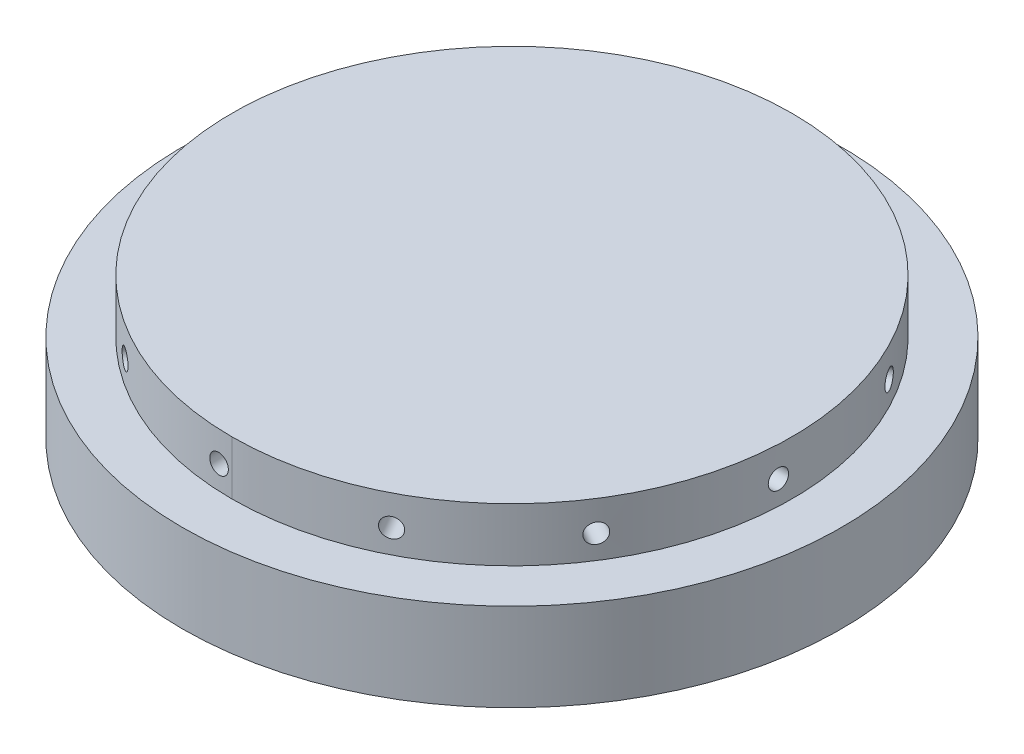
SolidWorks part; units mm, degrees
ref_plane "Front Plane" through (0, 0, 0) normal (0, 0, 1) x (1, 0, 0)
ref_plane "Top Plane" through (0, 0, 0) normal (0, 1, 0) x (1, 0, 0)
ref_plane "Right Plane" through (0, 0, 0) normal (1, 0, 0) x (0, 0, -1)
sketch "Sketch1" plane through (0, 0, 0) normal (0, 1, 0) x (1, 0, 0)
  circle A0 centre (0, 0) radius 64.77
  circle A1 centre (0, 0) radius 76.2
  circle A2 centre (0, 0) radius 56.1975
  circle A4 centre (0, 0) radius 62.865
  dimension "D1" = 152.4
  dimension "D3" = 112.395
  dimension "D2" = 129.54
  dimension "D4" = 13.335
extrude "Boss-Extrude1" add sketch "Sketch1" along normal blind 17.526 contours A0 A2 | A0 A4 region at (-62.938, 0, 0) region at (-61.0869, 0, 0)
extrude "Boss-Extrude2" add sketch "Sketch1<4>" along normal blind 5.08 and the other way blind 15.24 contours A1 A0 | A0 A4 region at (-62.938, 0, 0) region at (-74.0447, 0, 0)
sketch "Sketch1<4>" plane through (0, 0, 0) normal (0, 1, 0) x (1, 0, 0) same geometry as "Sketch1"
sketch "Sketch3" plane through (0, -15.24, 0) normal (0, -1, 0) x (1, 0, 0)
  line L0 (0, 0) -> (-65.7887, 5.7558) construction
  line L1 (0, 0) -> (0, 69.85) construction
  line L2 (0, 0) -> (48.9804, 58.3726)
  line L3 (0, 0) -> (13.232, 75.0424)
  line L4 (-13.335, -54.5925) -> (-13.335, -60.117)
  line L5 (13.335, -54.5925) -> (13.335, -60.117)
  line L6 (-13.335, -60.117) -> (13.335, -60.117)
  line L7 (-13.335, -60.117) -> (-13.335, -61.4344)
  line L8 (-23.7501, -50.9322) -> (-26.5679, -56.975)
  line L9 (0, 0) -> (-23.7501, -50.9322) construction
  line L10 (-65.2934, 11.4174) -> (-61.874, 11.1182)
  line L11 (-66.284, 0.0941) -> (-62.8647, -0.205)
  line L12 (-66.0236, -5.8708) -> (-62.6433, -5.2748)
  line L13 (-64.0498, -17.0646) -> (-60.6695, -16.4686)
  line L14 (-65.0367, -11.4677) -> (0, 0) construction
  line L15 (27.9275, 60.1135) -> (26.7536, 56.8881)
  line L16 (17.2465, 64.0011) -> (16.0725, 60.7757)
  line L17 (38.0961, -54.2427) -> (35.8898, -51.6133)
  line L18 (46.8033, -46.9365) -> (44.597, -44.3071)
  line L19 (-3.0468, 69.7835) -> (0, 0) construction
  line L20 (0, 0) -> (-21.0043, 66.6171) construction
  circle A0 centre (-65.7887, 5.7558) radius 5.6833
  circle A1 centre (-3.0468, 69.7835) radius 1.3589
  circle A2 centre (0, 0) radius 76.2 construction
  circle A5 centre (0, 0) radius 56.1975 construction
  arc A7 (-26.5679, -56.975) -> (-13.335, -61.4344) centre (0, 0) ccw
  arc A9 (-23.7501, -50.9322) -> (-13.335, -54.5925) centre (0, 0) ccw
  circle A10 centre (-65.7887, 5.7558) radius 2.5083
  circle A11 centre (-65.0367, -11.4677) radius 5.6832
  circle A13 centre (-65.0367, -11.4677) radius 2.5082
  circle A14 centre (0, 0) radius 62.865 construction
  circle A15 centre (22.587, 62.0573) radius 5.6832
  circle A16 centre (22.587, 62.0573) radius 2.5082
  circle A17 centre (42.4497, -50.5896) radius 5.6832
  circle A18 centre (42.4497, -50.5896) radius 2.5082
  arc A19 (-62.6433, -5.2748) -> (-60.6695, -16.4686) centre (0, 0) ccw
  circle A20 centre (-21.0043, 66.6171) radius 1.5
  circle A21 centre (0, 0) radius 62.865
  point P0 (0, -60.117)
  point P38 (0, 0)
  point P56 (0, 0)
  circle M49 centre (0, 0) radius 62.865
  dimension "D4" = 11.3665
  dimension "D5" = 2.7178
  dimension "D11" = 5.0165
  dimension "D17" = 3
  dimension "D1" = 66.04
  dimension "D3" = 69.85
  dimension "D6" = 30
  dimension "D7" = 10
  dimension "D9" = 26.67
  dimension "D8" = 5.5245
  dimension "D10" = 25
  dimension "D2" = 82.5
  dimension "D15" = 2.5
  dimension "D16" = 15
  dimension "D12" = 15
  dimension "D14" = 3
extrude "Cut-Extrude1" cut sketch "Sketch3" against normal blind 1.8415 contours A11 A13 M49 | A11 L13 M49 | A13 | A11 L12 M49 | A0 A10 M49 | A10 | A0 L11 M49 | A0 L10 M49 region at (-62.774, -15.24, 10.8743) region at (-63.6243, -15.24, 10.8507) region at (-63.7086, -15.24, 0.1915) region at (-63.4495, -15.24, -5.7433) region at (-64.265, -15.24, -5.9885) region at (-61.5874, -15.24, -16.304) region at (-65.7887, -15.24, 5.7558) region at (-65.0367, -15.24, -11.4677)
extrude "Cut-Extrude2" cut sketch "Sketch3<3>" against normal blind 12.7 contours A1 region at (-3.0468, -15.24, 69.7835)
sketch "Sketch3<3>" plane through (0, -15.24, 0) normal (0, -1, 0) x (1, 0, 0) same geometry as "Sketch3"
sketch "Sketch6" plane through (0, -13.3985, 0) normal (0, -1, 0) x (1, 0, 0)
  line L0 (-65.0367, -11.4677) -> (0, 0) construction
  line L1 (0, 0) -> (-65.7887, 5.7558) construction
  arc A0 (-65.2934, 11.4174) -> (-66.284, 0.0941) centre (-65.7887, 5.7558) ccw construction
  arc A1 (-65.2934, 11.4174) -> (-66.284, 0.0941) centre (-65.7887, 5.7558) ccw
  circle A2 centre (-65.7887, 5.7558) radius 2.5083
  circle A3 centre (-65.0367, -11.4677) radius 2.5082
  point P9 (0, 0)
  dimension "D1" = 5.0165
  dimension "D3" = 15
  dimension "D2" = 2
extrude "Cut-Extrude4" cut sketch "Sketch6" against normal blind 12.5095 contours A3 | A2 region at (-65.0367, -13.3985, -11.4677)
pattern_circular "CirPattern2" count 12 over 360 about axis through (0, -15.24, 0) along (0, 1, 0) of "Cut-Extrude2"
ref_plane "Plane1" through (0, 0, 76.2) normal (0, 0, 1) x (1, 0, 0)
sketch "Sketch5" plane through (0, 0, 76.2) normal (0, 0, 1) x (1, 0, 0)
  line L0 (-3.0468, -15.24) -> (-3.0468, 10.5664) construction
  line L1 (-4.4057, -15.24) -> (-1.6879, -15.24) construction
  line L3 (-76.2, -15.24) -> (76.2, -15.24) construction
  line L4 (76.2, 5.08) -> (-76.2, 5.08) construction
  line L5 (-76.2, -15.24) -> (76.2, -15.24)
  line L6 (76.2, 5.08) -> (-76.2, 5.08)
  circle A0 centre (-3.0468, 10.5664) radius 2.2479
  dimension "D2" = 4.4958
  dimension "D1" = 5.4864
extrude "Cut-Extrude3" cut sketch "Sketch5" against normal up to surface (20.0082 mm away) contours A0 region at (-3.0468, 10.5664, 76.2) up to face at (0, 17.526, 56.1975)
extrude "Boss-Extrude3" add sketch "Sketch3<11>" along normal blind 10.16 from surface contours L4 A9 L8 A7 L7 starting at face at (0, 0, 56.1975)
sketch "Sketch3<11>" plane through (0, -15.24, 0) normal (0, -1, 0) x (1, 0, 0) same geometry as "Sketch3"
pattern_circular "CirPattern3" count 6 over 360 about axis through (0, 17.526, 0) along (0, 1, 0) of "Boss-Extrude3"
fillet "Fillet1" radius 1.5875 12 edges at (-62.6258, -5.08, -5.479) (-59.8713, -5.08, -19.1688) (-26.5679, -5.08, -56.975) (-13.335, -5.08, -61.4344) (36.0579, -5.08, -51.496) (46.5363, -5.08, -42.2657) (62.6258, -5.08, 5.479) (59.8713, -5.08, 19.1688) (26.5679, -5.08, 56.975) (13.335, -5.08, 61.4344) (-36.0579, -5.08, 51.496) (-46.5363, -5.08, 42.2657)
pattern_circular "CirPattern4" count 12 over 360 about axis through (0, 17.526, 0) along (0, 1, 0) of "Cut-Extrude3"
sketch "Sketch8" plane through (0, 17.526, 0) normal (0, 1, 0) x (1, 0, 0)
  arc A0 (-34.7117, -52.4129) -> (12.0518, -61.699) centre (0, 0) ccw construction
  arc A1 (-34.7117, -52.4129) -> (12.0518, -61.699) centre (0, 0) ccw
  circle A2 centre (0, 0) radius 62.865
  circle M2 centre (0, 0) radius 56.1975
extrude "Cut-Extrude5" [suppressed] cut sketch "Sketch8" against normal up to surface (17.526 mm away) contours A1 A2 M2
sketch "Sketch9" plane through (0, 0, 0) normal (0, 0, 1) x (1, 0, 0)
  line L0 (0, 5.08) -> (0, 17.526)
  line L1 (76.2, 5.08) -> (-76.2, 5.08) construction
  line L2 (64.77, 17.526) -> (-64.77, 17.526) construction
split line "Split Line2"
extrude "Cut-Extrude7" cut sketch "Sketch3<24>" against normal blind 7.9375 contours A20
sketch "Sketch3<24>" plane through (0, -15.24, 0) normal (0, -1, 0) x (1, 0, 0) same geometry as "Sketch3"
pattern_circular "CirPattern1" count 3 over 360 about axis through (0, -15.24, 0) along (0, 1, 0) of "Cut-Extrude1", "Cut-Extrude4", "Cut-Extrude7"
extrude "Boss-Extrude4" add sketch "Sketch1<8>" along normal up to surface (17.526 mm away) contours A2 region at (0, 0, 0) up to face at (0, 17.526, 56.1975)
sketch "Sketch1<8>" plane through (0, 0, 0) normal (0, 1, 0) x (1, 0, 0) same geometry as "Sketch1"
equation "\"Middle Coupler Inner Daimeter\"= 3.875in"
equation "\"Middle Coupler  Wall Thickness\" = 0.25in"
equation "\"Middle Coupler Bottom Thickness\"= 0.2in"
equation "\"Bearing Rail Offset\"= 0.45in"
equation "\"3-56 UNF Tap\"= 0.089in"
equation "\"3-48 Tap\"= 0.079in"
equation "\"3-56 UNF Clearance\"= 0.104in"
equation "\"3-48 Clearance\" = 0.104in"
equation "\"Ball Bearing Distance\"= 0.03in"
equation "\"TCA Outer Diameter\" = 6in"
equation "\"Interstage Aeroframe Wall Thickness\" = 0.072in"
equation "\"Compression Spring OD\"= 0.42in"
equation "\"10-24 Tap\"= 0.1495in"
equation "\"10-24 Clearance\"= 0.196in"
equation "\"Lower Stage Fuselage Wall Thickness\" = 0.25in"
equation "\"6-32 Tap\" = 0.107in"
equation "\"6-32 Clearance\" = 0.144in"
equation "\"1/4-20 Tap\" = 0.201in"
equation "\"12-24 Tap\" = 0.177in"
equation "\"D1@Sketch1\"=\"TCA Outer Diameter\""
equation "\"D5@Sketch3\"=\"6-32 Tap\""
equation "\"D2@Sketch5\"=\"12-24 Tap\""
equation "\"D8@Sketch3\"=3/16+0.03"
equation "\"D3@Sketch1\"=\"Middle Coupler Inner Daimeter\" + 0.55"
equation "\"D1@Boss-Extrude1\"=0.15 + \"12-24 Major Diameter\"*2.5"
equation "\"12-24 Major Diameter\"= 0.216in"
equation "\"D1@Cut-Extrude1\"=1/16 + 0.01"
equation "\"D11@Sketch3\"=3/16 + 0.01"
equation "\"D1@Sketch6\"=3/16 + 0.01"
equation "\"D1@Sketch5\"=\"12-24 Major Diameter\""
equation "\"D1@Cut-Extrude4\"=0.4425+0.05"
